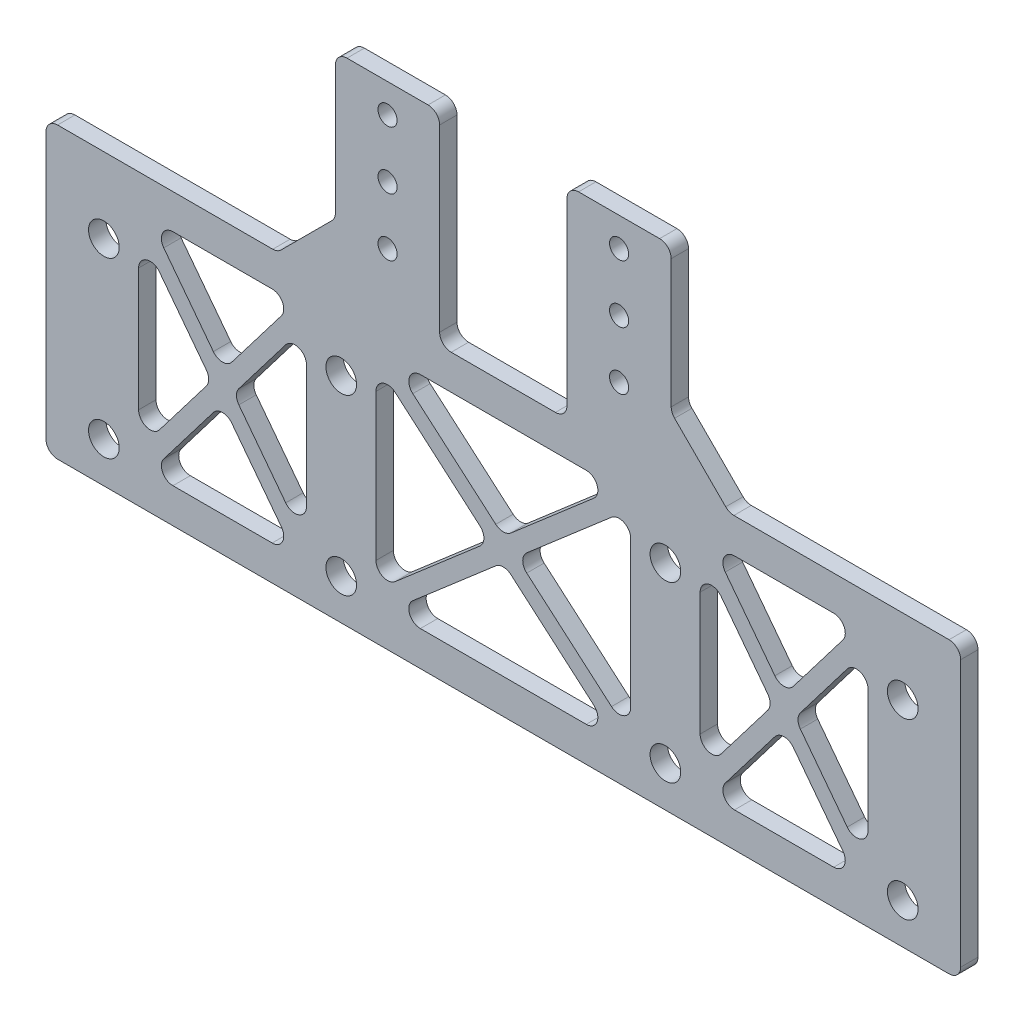
SolidWorks part; units mm, degrees
material "Thornel Mat VMA"
ref_plane "前视基准面" through (0, 0, 0) normal (0, 0, 1) x (1, 0, 0)
ref_plane "上视基准面" through (0, 0, 0) normal (0, 1, 0) x (1, 0, 0)
ref_plane "右视基准面" through (0, 0, 0) normal (1, 0, 0) x (0, 0, -1)
other "Configuration Table"
sketch "草图1" plane through (0, 0, 0) normal (0, 0, 1) x (1, 0, 0)
  line L0 (-10, 50) -> (-10, 85)
  line L1 (-10, 85) -> (10, 85)
  line L2 (-10, 50) -> (-79, 50)
  line L3 (-79, 50) -> (-79, 0)
  line L4 (0, 0) -> (0, 120.7371) construction
  line L5 (10, 50) -> (79, 50)
  line L6 (79, 50) -> (79, 0)
  line L7 (10, 50) -> (10, 85)
  line L8 (-79, 0) -> (79, 0)
  line L9 (-34, 6) -> (-34, 44)
  line L10 (63, 6) -> (34, 6)
  line L11 (63, 6) -> (63, 44)
  line L12 (63, 44) -> (34, 44)
  line L13 (34, 6) -> (34, 44)
  line L14 (63, 6) -> (34, 44) construction
  line L15 (63, 44) -> (34, 6) construction
  line L16 (22, 6) -> (-22, 6)
  line L17 (22, 6) -> (22, 44)
  line L18 (22, 44) -> (-22, 44)
  line L19 (-22, 6) -> (-22, 44)
  line L20 (22, 6) -> (-22, 44) construction
  line L21 (22, 44) -> (-22, 6) construction
  line L22 (-63, 6) -> (-34, 6)
  line L23 (-63, 6) -> (-63, 44)
  line L24 (-63, 44) -> (-34, 44)
  circle A0 centre (-6, 81) radius 1.55
  circle A1 centre (6, 81) radius 1.55
  circle A2 centre (-6, 59) radius 1.55
  circle A3 centre (6, 59) radius 1.55
  circle A4 centre (-69, 37) radius 2.65
  circle A5 centre (-69, 7) radius 2.65
  circle A6 centre (69, 7) radius 2.65
  circle A7 centre (69, 37) radius 2.65
  circle A8 centre (-28, 37) radius 2.65
  circle A9 centre (-28, 7) radius 2.65
  circle A10 centre (28, 7) radius 2.65
  circle A11 centre (28, 37) radius 2.65
  point P25 (48.5, 25)
  point P40 (0, 25)
  dimension "D3" = 3.1
  dimension "D4" = 4
  dimension "D5" = 22
  dimension "D6" = 4
  dimension "D8" = 30
  dimension "D10" = 5.3
  dimension "D11" = 138
  dimension "D12" = 41
  dimension "D14" = 6
  dimension "D1" = 85
  dimension "D2" = 35
  dimension "D7" = 20
  dimension "D9" = 13
  dimension "D13" = 10
  dimension "D15" = 6
  dimension "D16" = 6
  dimension "D17" = 6
  dimension "D18" = 6
  dimension "D19" = 6
  dimension "D20" = 6
extrude "凸台-拉伸1" add sketch "草图1" along normal blind 3
sketch "草图4" plane through (0, 0, 0) normal (0, 0, -1) x (-1, 0, 0)
  line L1 (-10, 85) -> (10, 85)
  line L2 (-10, 85) -> (-10, 50)
  line L3 (-10, 50) -> (10, 50)
  line L4 (10, 85) -> (10, 50)
  line L5 (-10, 85) -> (10, 50) construction
  line L6 (-10, 50) -> (10, 85) construction
  point P4 (0, 67.5)
extrude "切除-拉伸1" cut sketch "草图4" against normal blind 10
sketch "草图3" plane through (0, 0, 0) normal (0, 0, -1) x (-1, 0, 0)
  line L0 (0, 0) -> (0, 107.6848) construction
  line L1 (-79, 50) -> (79, 50) construction
  line L2 (-29, 85) -> (-11, 85)
  line L3 (-29, 85) -> (-29, 50)
  line L4 (-29, 50) -> (-11, 50)
  line L5 (-11, 85) -> (-11, 50)
  line L6 (-29, 85) -> (-11, 50) construction
  line L7 (-29, 50) -> (-11, 85) construction
  line L8 (29, 50) -> (11, 50)
  line L9 (11, 85) -> (11, 50)
  line L10 (29, 85) -> (11, 85)
  line L11 (29, 85) -> (29, 50)
  line L12 (29, 50) -> (11, 85) construction
  line L13 (29, 85) -> (11, 50) construction
  point P3 (-20, 67.5)
  point P14 (20, 67.5)
  dimension "D1" = 22
  dimension "D2" = 18
  dimension "D3" = 35
extrude "凸台-拉伸2" add sketch "草图3" against normal blind 3
sketch "草图5" plane through (0, 0, 0) normal (0, 0, -1) x (-1, 0, 0)
  line L0 (-20, 85) -> (-20, 49.8355) construction
  line L1 (-11, 85) -> (-29, 85) construction
  line L2 (-11, 50) -> (-11, 85) construction
  line L3 (-20, 80) -> (-20, 70) construction
  line L4 (0, 0) -> (0, 108.4309) construction
  circle A0 centre (-20, 80) radius 1.65
  circle A1 centre (-20, 70) radius 1.65
  circle A2 centre (-20, 60) radius 1.65
  circle A5 centre (20, 60) radius 1.65
  circle A6 centre (20, 70) radius 1.65
  circle A7 centre (20, 80) radius 1.65
  dimension "D5" = 3.3
  dimension "D1" = 9
  dimension "D2" = 5
  dimension "D4" = 10
  dimension "D3" = 3
extrude "切除-拉伸2" cut sketch "草图5" against normal blind 5
chamfer "倒角1" distance 10 angle 45 2 edges at (-29, 50, 1.5) (29, 50, 1.5)
fillet "圆角1" radius 2 14 edges at (79, 0, 1.5) (-79, 0, 1.5) (-79, 50, 1.5) (-39, 50, 1.5) (-29, 60, 1.5) (-29, 85, 1.5) (-11, 85, 1.5) (-11, 50, 1.5) (11, 50, 1.5) (11, 85, 1.5) (29, 85, 1.5) (39, 50, 1.5) (79, 50, 1.5) (29, 60, 1.5)
sketch "草图6" plane through (0, 0, 0) normal (0, 0, -1) x (-1, 0, 0)
  line L0 (-63, 44) -> (-34, 6)
  line L1 (-34, 44) -> (-63, 6)
  line L2 (-22, 44) -> (22, 6)
  line L3 (22, 44) -> (-22, 6)
  line L4 (34, 44) -> (63, 6)
  line L5 (63, 44) -> (34, 6)
  line L6 (63, 6) -> (34, 6) construction
  line L7 (34, 6) -> (34, 44) construction
extrude "拉伸-薄壁1" add sketch "草图6" against normal blind 3 thin thin type mid plane wall 3
fillet "圆角3" radius 2 36 edges at (0, 23.018, 1.5) (19.7051, 6, 1.5) (-19.7051, 6, 1.5) (-22, 42.018, 1.5) (-2.2949, 25, 1.5) (-22, 7.982, 1.5) (22, 7.982, 1.5) (2.2949, 25, 1.5) (22, 42.018, 1.5) (0, 26.982, 1.5) (-19.7051, 44, 1.5) (19.7051, 44, 1.5) (48.5, 27.4725, 1.5) (35.8869, 44, 1.5) (61.1131, 44, 1.5) (63, 8.4725, 1.5) (50.3869, 25, 1.5) (34, 41.5275, 1.5) (46.6131, 25, 1.5) (34, 8.4725, 1.5) (48.5, 22.5275, 1.5) (61.1131, 6, 1.5) (35.8869, 6, 1.5) (-48.5, 27.4725, 1.5) (-61.1131, 44, 1.5) (-35.8869, 44, 1.5) (-34, 8.4725, 1.5) (-46.6131, 25, 1.5) (-34, 41.5275, 1.5) (-63, 41.5275, 1.5) (-50.3869, 25, 1.5) (-63, 8.4725, 1.5) (-48.5, 22.5275, 1.5) (-35.8869, 6, 1.5) (-61.1131, 6, 1.5) (63, 41.5275, 1.5)
